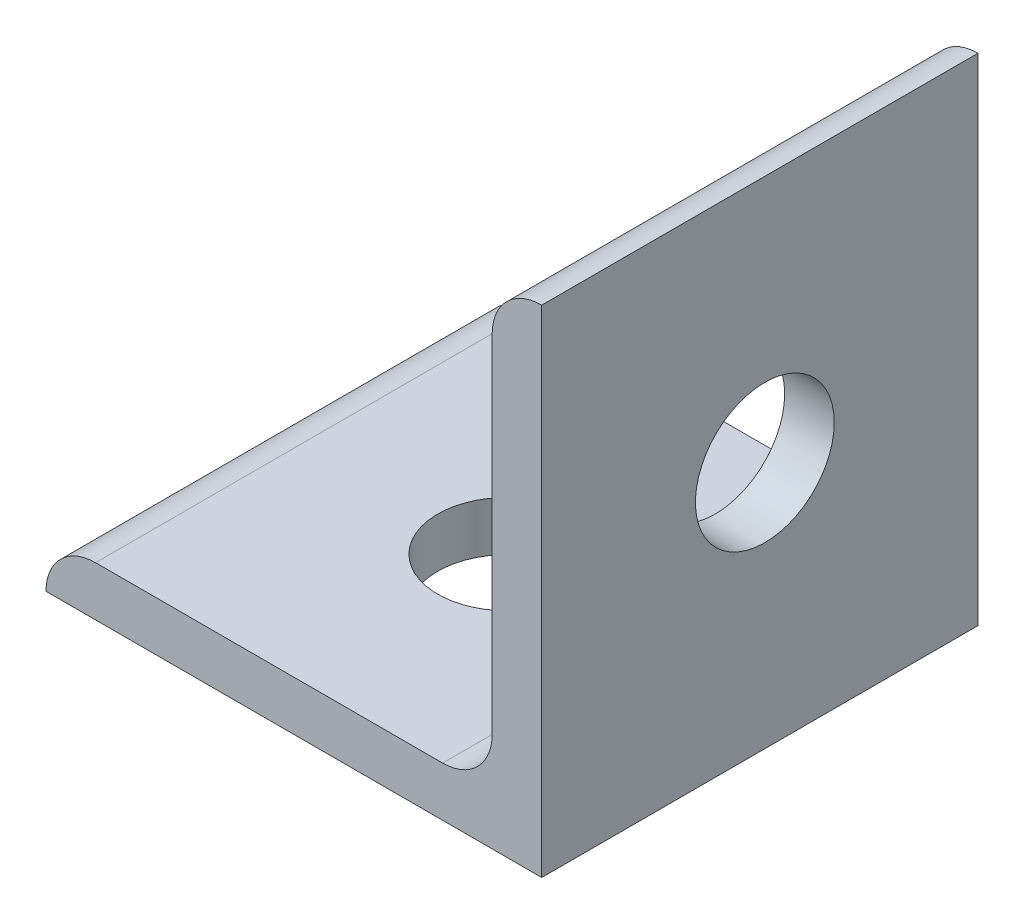
SolidWorks part; units mm, degrees
ref_plane "Front Plane" through (0, 0, 0) normal (0, 0, 1) x (1, 0, 0)
ref_plane "Top Plane" through (0, 0, 0) normal (0, 1, 0) x (1, 0, 0)
ref_plane "Right Plane" through (0, 0, 0) normal (1, 0, 0) x (0, 0, -1)
sketch "Sketch1" plane through (0, 0, 0) normal (0, 0, 1) x (1, 0, 0)
  line L0 (-11.43, -11.43) -> (11.43, -11.43)
  line L1 (11.43, -11.43) -> (11.43, 11.43)
  line L2 (-11.43, -11.43) -> (11.43, 11.43) construction
  dimension "D1" = 22.86
extrude "Extrude-Thin1" add sketch "Sketch1" along normal blind 22.352 thin thin type one direction wall 2.54
fillet "Fillet1" radius 2.54 3 edges at (11.43, 11.43, 11.176) (-11.43, -11.43, 11.176) (11.43, -11.43, 11.176)
sketch "Sketch2" plane through (0, -13.97, 0) normal (0, -1, 0) x (1, 0, 0)
  line L0 (13.97, 22.352) -> (13.97, 0) construction
  line L1 (-11.43, 0) -> (13.97, 0) construction
  circle A0 centre (1.27, 11.43) radius 3.556
  dimension "D1" = 7.112
  dimension "D2" = 12.7
  dimension "D3" = 11.43
extrude "Cut-Extrude1" cut sketch "Sketch2" against normal blind 2.54
sketch "Sketch3" plane through (13.97, 0, 0) normal (1, 0, 0) x (0, 0, -1)
  line L0 (-22.352, -13.97) -> (0, -13.97) construction
  line L1 (-22.352, -13.97) -> (-22.352, 11.43) construction
  circle A0 centre (-10.922, -1.27) radius 3.556
  dimension "D1" = 7.112
  dimension "D2" = 12.7
  dimension "D3" = 11.43
extrude "Cut-Extrude2" cut sketch "Sketch3" against normal blind 2.54
